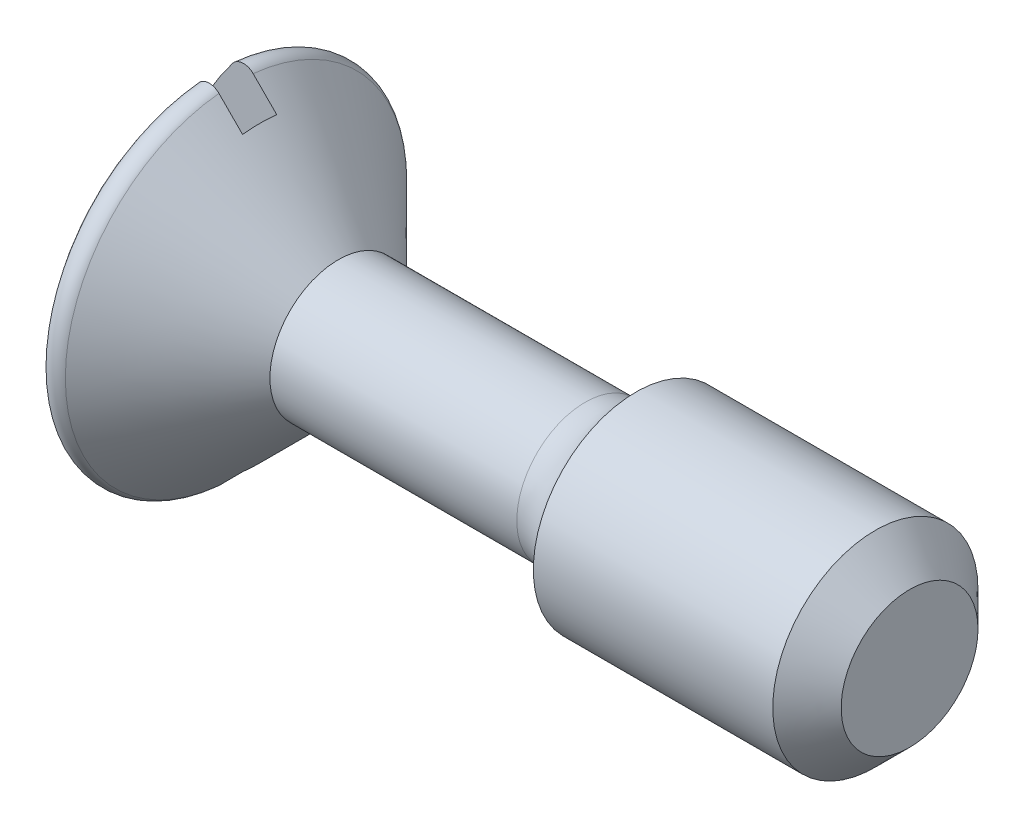
SolidWorks part; units mm, degrees
ref_plane "Front" through (0, 0, 0) normal (0, 0, 1) x (1, 0, 0)
ref_plane "Top" through (0, 0, 0) normal (0, 1, 0) x (1, 0, 0)
ref_plane "Right" through (0, 0, 0) normal (1, 0, 0) x (0, 0, -1)
ref_plane "Plane1" through (1.65, 0, 0) normal (1, 0, 0) x (0, 0, -1)
sketch "Sketch1" plane through (1.65, 0, 0) normal (1, 0, 0) x (0, 0, -1)
  line L0 (0, 0) -> (10, 0) construction
  circle A0 centre (0, 0) radius 1
  dimension "l" = 10
extrude "BaseHead" add sketch "Sketch1" against normal blind 1.65 draft 45 draft outward yes
sketch "Sketch2" plane through (1.65, 0.5934, 0.2449) normal (1, 0, 0) x (0, 0, -1)
  circle A0 centre (0.2449, -0.5934) radius 1
  circle A1 centre (0.2449, -0.5934) radius 1 construction
extrude "BaseBody" add sketch "Sketch2" along normal blind 8.35
dome "BaseTop" faces to dome 1 distance 1 reverse direction no elliptical dome no face at (0, 0, -2.65) parameters "f"=1
sketch "Sketch3" plane through (1.9, 0, 1.9) normal (0, 1, 0) x (0, 0, 1)
  line L1 (-2.15, -1.4) -> (-1.65, -1.4)
  line L2 (-2.15, -1.4) -> (-2.15, -2.9)
  line L3 (-2.15, -2.9) -> (-1.65, -2.9)
  line L4 (-1.65, -1.4) -> (-1.65, -2.9)
  arc A0 (-4.55, -1.9) -> (0.75, -1.9) centre (-1.9, 1.1113) ccw construction
  arc A1 (-4.55, -1.9) -> (0.75, -1.9) centre (-1.9, 1.1113) ccw construction
  dimension "t" = 1.5
  dimension "m" = 0.25
extrude "Slot" cut sketch "Sketch3" against normal through all and the other way through all
sketch "Sketch4" plane through (10, -0.1385, -0.1649) normal (1, 0, 0) x (0, 0, -1)
  circle A0 centre (-0.1649, 0.1385) radius 1.5
  circle A1 centre (-0.1649, 0.1385) radius 1 construction
extrude "BaseEnd" add sketch "Sketch4" against normal blind 4
cosmetic thread "ThreadCosmetic1" [suppressed] parameters "THD_MINOR"=1.75
chamfer "Chamfer1" distance 0.5 angle 45 1 edges at (10, 0, -1.5)
fillet "Fillet1" radius 0.8 1 edges at (6, 0, -1)
fillet "Fillet2" radius 0.2 2 edges at (0, 0, 2.65) (0, 0, -2.65)
sketch "Sketch5" plane through (0, 0, 0) normal (0, 0, 1) x (1, 0, 0)
  line L0 (6, 0.9587) -> (6.3125, 1.5)
  line L1 (6.3125, 1.5) -> (6.3125, 2.125)
  line L2 (6.3125, 2.125) -> (5.6875, 2.125)
  line L3 (5.6875, 2.125) -> (5.6875, 1.5)
  line L4 (5.6875, 1.5) -> (6, 0.9587)
  line L5 (0, 0) -> (6.856, 0) construction
  line L6 (10, -1) -> (10, 1) construction
  dimension "D1" = 3
  dimension "D2" = 0.625
  dimension "D3" = 4
revolve "Cut-Revolve10" [suppressed] cut sketch "Sketch5" angle 360 about L5
pattern_linear "LPattern10" [suppressed] count 5 spacing 0.75 along (1, 0, 0) of bodies 105
equation "\"m@Sketch3\" = \"n@Sketch3\" / 2"
equation "\"D1@Plane1\"=\"k@BaseHead\""
equation "\"l@BaseBody\" = \"l@Sketch1\" - \"k@BaseHead\""
equation "\"D1@Sketch5\" = \"d@Sketch4\""
equation "\"D3@Sketch5\" = \"b@BaseEnd\""
equation "\"D2@Sketch5\" =  ( \"d@Sketch4\" - \"THD_MINOR@ThreadCosmetic1\" )  / 2"
equation "\"D3@LPattern10\" = \"D2@Sketch5\" * 1.2"
equation "\"D1@LPattern10\" = \"b@BaseEnd\" / \"D3@LPattern10\""
